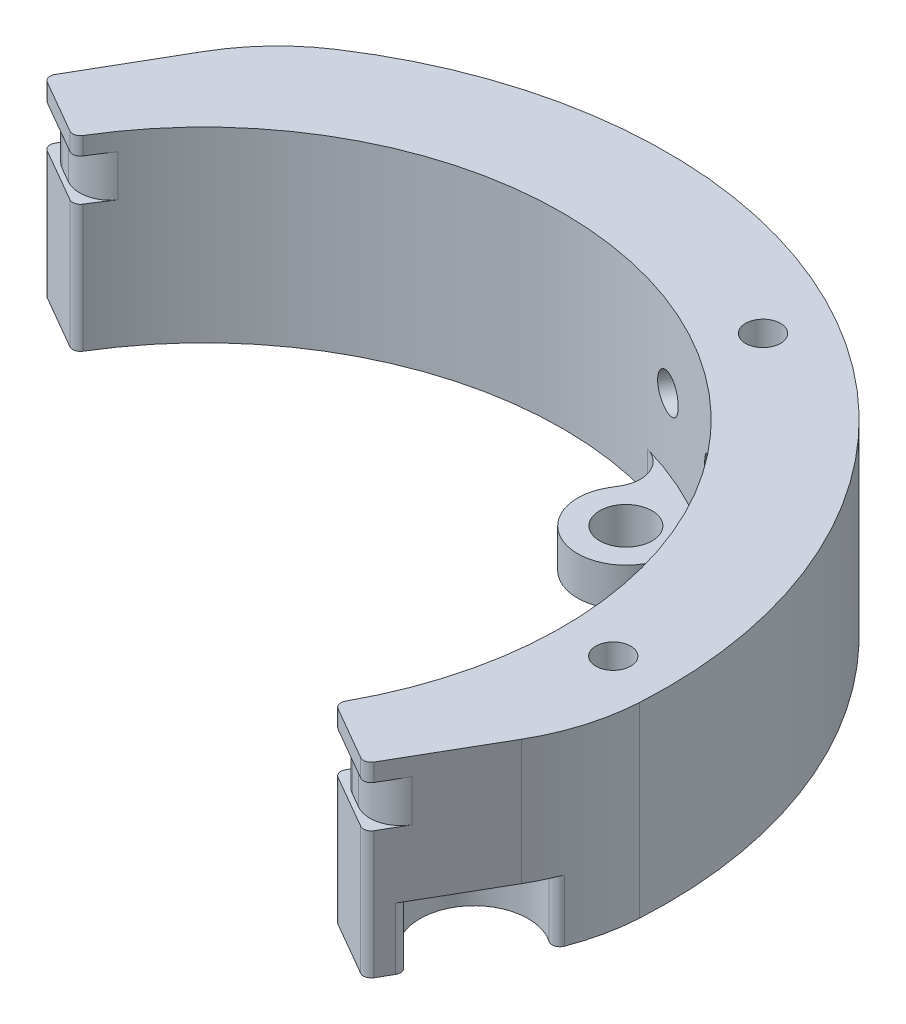
SolidWorks part; units mm, degrees
material "ABS"
ref_plane "Front Plane" through (0, 0, 0) normal (0, 0, 1) x (1, 0, 0)
ref_plane "Top Plane" through (0, 0, 0) normal (0, 1, 0) x (1, 0, 0)
ref_plane "Right Plane" through (0, 0, 0) normal (1, 0, 0) x (0, 0, -1)
sketch "Sketch1" plane through (0, 0, 0) normal (0, 1, 0) x (1, 0, 0)
  line L0 (26.5022, -23.3607) -> (0, 0) construction
  line L5 (0, 0) -> (-26.5022, -23.3607) construction
  line L6 (0, 0) -> (0, -41.0991) construction
  line L7 (0, 0) -> (-22.3838, -38.7698) construction
  line L8 (0, 0) -> (-36.4505, -25.9903) construction
  line L9 (-39.6834, -25.8001) -> (-38.0343, 2.2371) construction
  line L10 (0, 0) -> (-24.7896, -37.2774) construction
  line L11 (-35.8055, 9.6738) -> (-31.043, 17.9227)
  line L14 (26.2805, -26.1716) -> (31.043, -17.9227)
  line L16 (31.043, -17.9227) -> (-31.043, 17.9227) construction
  line L17 (-31.043, 17.9227) -> (-25.5438, 14.7477)
  line L18 (25.5438, -14.7477) -> (31.043, -17.9227)
  line L19 (-24.7896, -37.2774) -> (-22.3838, -38.7698) construction
  circle A0 centre (0, 0) radius 12.5 construction
  circle A9 centre (0, 0) radius 50.8 construction
  circle A16 centre (0, 0) radius 38.1 construction
  circle A17 centre (-22.3838, -38.7698) radius 5.3975 construction
  circle A18 centre (-22.3838, -38.7698) radius 3.2385 construction
  circle A19 centre (-36.4505, -25.9903) radius 3.2385 construction
  circle A20 centre (-36.4505, -25.9903) radius 5.3975 construction
  arc A21 (-38.0343, 2.2371) -> (20.9545, -31.8201) centre (0, 0) ccw
  arc A22 (-38.0343, 2.2371) -> (-35.8055, 9.6738) centre (-21.2109, 1.2476) cw
  arc A23 (20.9545, -31.8201) -> (26.2805, -26.1716) centre (11.6859, -17.7454) ccw
  arc A24 (-25.5438, 14.7477) -> (25.5438, -14.7477) centre (0, 0) ccw
  dimension "D2" = 25
  dimension "D3" = 76.2
  dimension "D4" = 97.21
  dimension "D5" = 30
  dimension "D6" = 10.795
  dimension "D9" = 101.6
  dimension "D10" = 24.51
  dimension "D11" = 6.477
  dimension "D12" = 9.525
  dimension "D8" = 1.27
  dimension "D13" = 6.35
  dimension "D7" = 35.3283
  dimension "D14" = 2.8312
  dimension "D15" = 44.7675
extrude "Boss-Extrude1" add sketch "Sketch1" along normal blind 15.367 contours A24 L17 L11 A22 A21 A23 L14 L18
sketch "Sketch8" plane through (0, 0, 0) normal (0, 1, 0) x (1, 0, 0)
  line L0 (-12.7, -21.997) -> (0, 0) construction
  line L2 (-9.263, -23.9814) -> (-11.1766, -27.2959)
  line L3 (-16.137, -20.0127) -> (-18.0506, -23.3271)
  line L4 (0, 0) -> (0, -29.4954) construction
  line L7 (0, 0) -> (-22.3838, -38.7698) construction
  line L8 (3.9688, -25.4) -> (3.9688, -29.2272)
  line L9 (-3.9687, -25.4) -> (-3.9687, -29.2272)
  arc A0 (-9.263, -23.9814) -> (-16.137, -20.0127) centre (-12.7, -21.997) ccw
  arc A1 (-3.9687, -25.4) -> (3.9688, -25.4) centre (0, -25.4) cw
  arc A3 (-18.0506, -23.3271) -> (-11.1766, -27.2959) centre (0, 0) ccw
  arc A5 (-25.5438, 14.7477) -> (25.5438, -14.7477) centre (0, 0) ccw construction
  arc A6 (-25.5438, 14.7477) -> (25.5438, -14.7477) centre (0, 0) ccw construction
  arc A7 (-3.9687, -29.2272) -> (3.9688, -29.2272) centre (0, 0) ccw
  dimension "D1" = 7.9375
  dimension "D2" = 25.4
extrude "Boss-Extrude2" add sketch "Sketch8" along normal blind 3.175
hole_wizard "#8 Clearance Hole1" positions "Sketch3" profile "Sketch4" hole size "#8" standard "ANSI Inch" end condition through all
sketch "Sketch3" plane through (0, 3.175, 0) normal (0, 1, 0) x (1, 0, 0)
  point P6 (0, -25.4)
  point P9 (-12.7, -21.997)
sketch "Sketch4" plane through (0, 3.175, 25.4) normal (1, 0, 0) x (0, 0, 1)
  line L0 (0, 0) -> (0, 3.175)
  line L1 (0, 3.175) -> (2.1526, 3.175)
  line L2 (2.1526, 3.175) -> (2.1526, 0)
  line L5 (2.1526, 0) -> (0, 0)
  line L11 (0, -6.35) -> (0, 107.95) construction
  dimension "Thru Hole Dia." = 4.3053
  dimension "Thru Hole Depth" = 3.175
sketch "Sketch10" plane through (0, 0, 0) normal (0, -1, 0) x (1, 0, 0)
  circle A0 centre (-26.5022, 23.3607) radius 4.445
  circle A1 centre (26.5022, 23.3607) radius 4.445
  dimension "D1" = 8.89
extrude "Cut-Extrude2" cut sketch "Sketch10" against normal blind 5.08
fillet "Fillet3" radius 2.54 6 edges at (-11.1766, 1.5875, 27.2959) (-18.0506, 1.5875, 23.3271) (-26.0696, 2.54, 27.7846) (-30.8368, 2.54, 22.3763) (-3.9687, 1.5875, 29.2272) (3.9688, 1.5875, 29.2272)
sketch "Sketch12" plane through (31.043, 0, 17.9227) normal (0.866, 0, 0.5) x (0.5, 0, -0.866)
  line L1 (0, 15.367) -> (0, 0) construction
  line L2 (-2.7037, 0) -> (0, 0) construction
  line L3 (0, 13.9065) -> (-0.381, 13.9065)
  line L4 (0, 13.9065) -> (0, 10.4775)
  line L5 (0, 10.4775) -> (-0.381, 10.4775)
  line L6 (-0.381, 13.9065) -> (-0.381, 10.4775)
  line L7 (0, 13.9065) -> (-0.381, 10.4775) construction
  line L8 (0, 10.4775) -> (-0.381, 13.9065) construction
  point P8 (-0.1905, 12.192)
  dimension "D1" = 0.381
  dimension "D2" = 12.192
  dimension "D3" = 3.429
extrude "Cut-Extrude5" cut sketch "Sketch12" against normal through all
fillet "Fillet6" radius 2.54 4 edges at (-25.7321, 12.192, -14.4165) (-31.2335, 12.192, -17.5928) (25.3511, 12.192, 15.0764) (30.8525, 12.192, 18.2527)
sketch "Sketch15" plane through (0, 0, 0) normal (0.5, 0, -0.866) x (-0.866, 0, -0.5)
  line L0 (-35.8454, 0) -> (35.8454, 0) construction
  line L1 (35.8454, 0) -> (35.8454, 15.367) construction
  line L2 (35.8454, 15.367) -> (35.8454, 13.9065) construction
  line L3 (35.8454, 15.367) -> (-35.8454, 15.367) construction
  line L4 (-35.8454, 15.367) -> (-35.8454, 0) construction
  line L6 (-35.8454, 8.89) -> (-4.445, 8.89) construction
  line L7 (-4.445, 8.89) -> (4.445, 8.89) construction
  line L8 (4.445, 8.89) -> (35.8454, 8.89) construction
  dimension "D1" = 8.89
  dimension "D2" = 8.89
hole_wizard "CBORE for #4 Socket Head Cap Screw1" positions "3DSketch1" profile "Sketch16" counterbore size "#4" standard "ANSI Inch" end condition up to next
sketch3d "3DSketch1"
  point P0 (-3.8495, 8.89, -2.2225)
  point P3 (3.8495, 8.89, 2.2225)
sketch "Sketch16" plane through (-3.8495, 8.89, -2.2225) normal (0, 1, 0) x (-0.866, 0, -0.5)
  line L0 (0, 0) -> (0, 37.8398)
  line L1 (2.7788, 37.8398) -> (2.7788, 34.995)
  line L2 (1.4732, 34.995) -> (1.4732, 2.8448)
  line L3 (1.4732, 2.8448) -> (2.7788, 2.8448)
  line L4 (2.7788, 2.8448) -> (2.7788, 0)
  line L5 (2.7788, 0) -> (0, 0)
  line L6 (2.7788, 34.995) -> (1.4732, 34.995)
  line L11 (0, -6.35) -> (0, 107.95) construction
  line L12 (2.7788, 37.8398) -> (0, 37.8398)
  dimension "Thru Hole Dia." = 2.9464
  dimension "Thru Hole Depth" = 37.8398
  dimension "C'Bore Dia." = 5.5575
  dimension "C'Bore Depth" = 2.8448
sketch "Sketch17" plane through (0, 15.367, 0) normal (0, 1, 0) x (1, 0, 0)
  line L0 (0, 0) -> (16.8275, -29.1461) construction
  line L1 (0, 0) -> (-16.8275, -29.1461) construction
  line L2 (0, 0) -> (0, -38.1) construction
  arc A0 (-38.0343, 2.2371) -> (20.9545, -31.8201) centre (0, 0) ccw construction
  circle A1 centre (-16.8275, -29.1461) radius 1.4351
  circle A2 centre (16.8275, -29.1461) radius 1.4351
  dimension "D4" = 2.8702
  dimension "D1" = 30
  dimension "D2" = 30
  dimension "D3" = 33.655
extrude "Cut-Extrude6" cut sketch "Sketch17" against normal up to next
fillet "Fillet7" radius 0.635 10 edges at (25.5438, 14.6368, 14.7477) (-31.043, 14.6368, -17.9227) (-25.5438, 14.6368, -14.7477) (31.043, 14.6368, 17.9227) (25.3231, 2.54, 27.6465) (29.6912, 2.54, 20.2642) (31.043, 5.2388, 17.9227) (25.5438, 5.2388, 14.7477) (-25.5438, 5.2388, -14.7477) (-31.043, 5.2388, -17.9227)
ref_plane "Plane1" through (1.27, 0, -2.1997) normal (0.5, 0, -0.866) x (-0.866, 0, -0.5)
mirror "Mirror4" about plane through (1.27, 0, -2.1997) normal (0.5, 0, -0.866) of bodies 118
sketch "Sketch18" plane through (0, 15.367, 0) normal (0, 1, 0) x (1, 0, 0)
  line L0 (-35.598, 20.5613) -> (38.4277, -19.5662)
  line L1 (38.4277, -19.5662) -> (10.3965, -40.4267)
  line L2 (10.3965, -40.4267) -> (-26.1818, -37.5294)
  line L3 (-26.1818, -37.5294) -> (-44.652, -8.1219)
  line L4 (-44.652, -8.1219) -> (-35.598, 20.5613)
extrude "Cut-Extrude7" cut sketch "Sketch18" against normal through all
